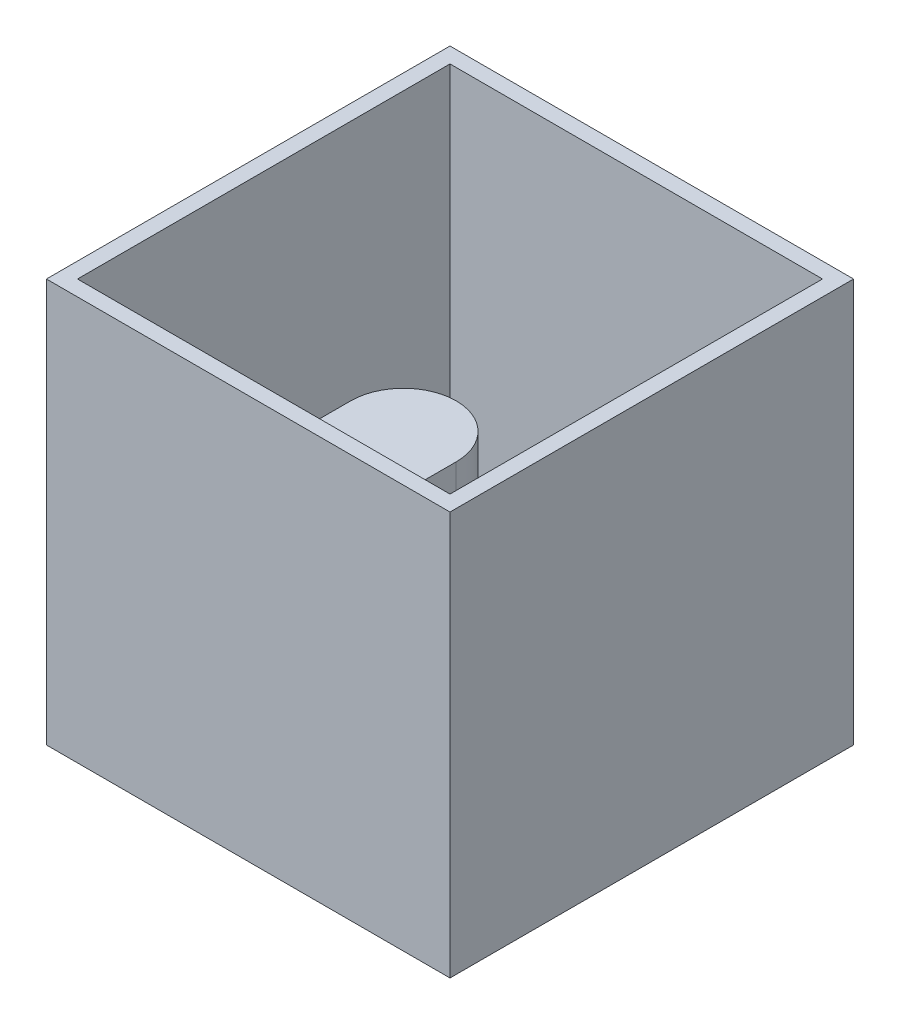
SolidWorks part; units mm, degrees
ref_plane "Front Plane" through (0, 0, 0) normal (0, 0, 1) x (1, 0, 0)
ref_plane "Top Plane" through (0, 0, 0) normal (0, 1, 0) x (1, 0, 0)
ref_plane "Right Plane" through (0, 0, 0) normal (1, 0, 0) x (0, 0, -1)
sketch "Sketch1" plane through (0, 0, 0) normal (0, 1, 0) x (1, 0, 0)
  line L0 (-1.5, -0.3414) -> (11.5, -0.3414)
  line L1 (-1, -12.8414) -> (11, -12.8414)
  line L2 (-1, -12.8414) -> (-1, -0.8414)
  line L3 (-1, -0.8414) -> (11, -0.8414)
  line L4 (11, -12.8414) -> (11, -0.8414)
  line L5 (-1, -12.8414) -> (11, -0.8414) construction
  line L6 (-1, -0.8414) -> (11, -12.8414) construction
  line L7 (-0.5, -2.8414) -> (5.5, -2.8414)
  line L8 (-0.5, -2.8414) -> (-0.5, -10.8414)
  line L9 (-0.5, -10.8414) -> (5.5, -10.8414)
  line L10 (5.5, -2.8414) -> (5.5, -10.8414)
  line L11 (-0.5, -2.8414) -> (5.5, -10.8414) construction
  line L12 (-0.5, -10.8414) -> (5.5, -2.8414) construction
  line L13 (5.5, -5.8449) -> (9.5, -5.8449)
  line L14 (5.5, -5.8449) -> (5.5, -7.5989)
  line L15 (5.5, -7.5989) -> (9.5, -7.5989)
  line L16 (9.5, -5.8449) -> (9.5, -7.5989)
  line L17 (5.5, -5.8449) -> (9.5, -7.5989) construction
  line L18 (5.5, -7.5989) -> (9.5, -5.8449) construction
  line L19 (11.5, -13.3414) -> (11.5, -0.3414)
  line L20 (-1.5, -13.3414) -> (11.5, -13.3414)
  line L21 (-1.5, -13.3414) -> (-1.5, -0.3414)
  point P0 (5, -6.8414)
  point P6 (2.5, -6.8414)
  point P11 (7.5, -6.7219)
  dimension "D1" = 12
  dimension "D2" = 12
  dimension "D3" = 0.8414
  dimension "D4" = 1
  dimension "D5" = 6
  dimension "D6" = 8
  dimension "D7" = 4
  dimension "D8" = 2
  dimension "D9" = 1.5
  dimension "D10" = 0
  dimension "D11" = 0.5
extrude "Boss-Extrude1" add sketch "Sketch1" along normal blind 13 contours L21 L20 L19 L0 L4 L1 L2 L3 region at (5, 0, 0.5253)
extrude "Boss-Extrude2" add sketch "Sketch1<4>" along normal blind 1 contours L1 L4 L3 L2 L13 L16 L15 L10 L9 L8 L7 | L10 L7 L8 L9 | L16 L13 L10 L15 region at (-0.8303, 0, 6.8414) region at (2.5, 0, 6.8414) region at (7.5, 0, 6.7219)
sketch "Sketch1<4>" plane through (0, 0, 0) normal (0, 1, 0) x (1, 0, 0) same geometry as "Sketch1"
extrude "Cut-Extrude1" cut sketch "Sketch1<7>" along normal blind 1 contours L10 L7 L8 L9 | L16 L13 L10 L15 region at (2.5, 0, 6.8414) region at (7.5, 0, 6.7219)
sketch "Sketch1<7>" plane through (0, 0, 0) normal (0, 1, 0) x (1, 0, 0) same geometry as "Sketch1"
fillet "Fillet1" radius 3 4 edges at (-0.5, 0.5, 2.8414) (5.5, 0.5, 2.8414) (5.5, 0.5, 10.8414) (-0.5, 0.5, 10.8414)
sketch "Sketch3" plane through (0, 0, 0) normal (0, -1, 0) x (1, 0, 0)
  line L1 (9.2, 7.2989) -> (10.2434, 7.2989)
  line L2 (9.2, 7.2989) -> (9.2, 6.1449)
  line L3 (9.2, 6.1449) -> (10.2434, 6.1449)
  line L4 (10.2434, 7.2989) -> (10.2434, 6.1449)
  line L5 (9.2, 7.2989) -> (10.2434, 6.1449) construction
  line L6 (9.2, 6.1449) -> (10.2434, 7.2989) construction
  line L35 (5.2, 5.8414) -> (5.2, 6.1449)
  line L36 (-0.2, 7.8414) -> (-0.2, 5.8414)
  line L37 (9.2, 6.1449) -> (9.2, 7.2989)
  line L38 (5.2, 6.1449) -> (9.2, 6.1449)
  line L39 (5.2, 7.2989) -> (5.2, 7.8414)
  line L40 (9.2, 7.2989) -> (5.2, 7.2989)
  line L41 (5.2, 5.8414) -> (5.2, 6.1449)
  line L42 (-0.2, 7.8414) -> (-0.2, 5.8414)
  line L43 (9.2, 6.1449) -> (9.2, 7.2989)
  line L44 (5.2, 6.1449) -> (9.2, 6.1449)
  line L45 (5.2, 7.2989) -> (5.2, 7.8414)
  line L46 (9.2, 7.2989) -> (5.2, 7.2989)
  arc A30 (-0.2, 5.8414) -> (2.5, 3.1414) centre (2.5, 5.8414) ccw
  arc A31 (2.5, 3.1414) -> (5.2, 5.8414) centre (2.5, 5.8414) ccw
  arc A32 (2.5, 10.5414) -> (-0.2, 7.8414) centre (2.5, 7.8414) ccw
  arc A33 (5.2, 7.8414) -> (2.5, 10.5414) centre (2.5, 7.8414) ccw
  arc A34 (-0.2, 5.8414) -> (2.5, 3.1414) centre (2.5, 5.8414) ccw
  arc A35 (2.5, 3.1414) -> (5.2, 5.8414) centre (2.5, 5.8414) ccw
  arc A36 (2.5, 10.5414) -> (-0.2, 7.8414) centre (2.5, 7.8414) ccw
  arc A37 (5.2, 7.8414) -> (2.5, 10.5414) centre (2.5, 7.8414) ccw
  point P2 (9.7217, 6.7219)
  line M21 (9.5, 7.5989) -> (9.5, 5.8449)
  dimension "D1" = 0.3
extrude "Boss-Extrude3" add sketch "Sketch3" against normal blind 1 contours L4 L1 L3 M21 | L45 A37 A36 L42 A34 A35 L41 L44 L2 L46 | L2 L3 L1 M21 region at (9.35, 0, 6.7219) region at (3.0662, 0, 6.827) region at (9.8717, 0, 6.7219)
fillet "Fillet2" radius 20 2 edges at (9.5, 0.5, 7.2989) (9.5, 0.5, 6.1449)
sketch "Sketch4" plane through (0, 1, 0) normal (0, 1, 0) x (1, 0, 0)
  line L1 (4.2, -5.8414) -> (4.2, -7.8414)
  line L2 (0.8, -5.8414) -> (0.8, -7.8414)
  line L3 (0.8, -5.8414) -> (0.8, -7.8414)
  arc A18 (0.8, -7.8414) -> (4.2, -7.8414) centre (2.5, -7.8414) ccw
  arc A19 (4.2, -5.8414) -> (0.8, -5.8414) centre (2.5, -5.8414) ccw
  arc A20 (0.8, -7.8414) -> (4.2, -7.8414) centre (2.5, -7.8414) ccw
  arc A21 (4.2, -5.8414) -> (0.8, -5.8414) centre (2.5, -5.8414) ccw
  dimension "D1" = 1
extrude "Boss-Extrude4" add sketch "Sketch4" along normal blind 6
